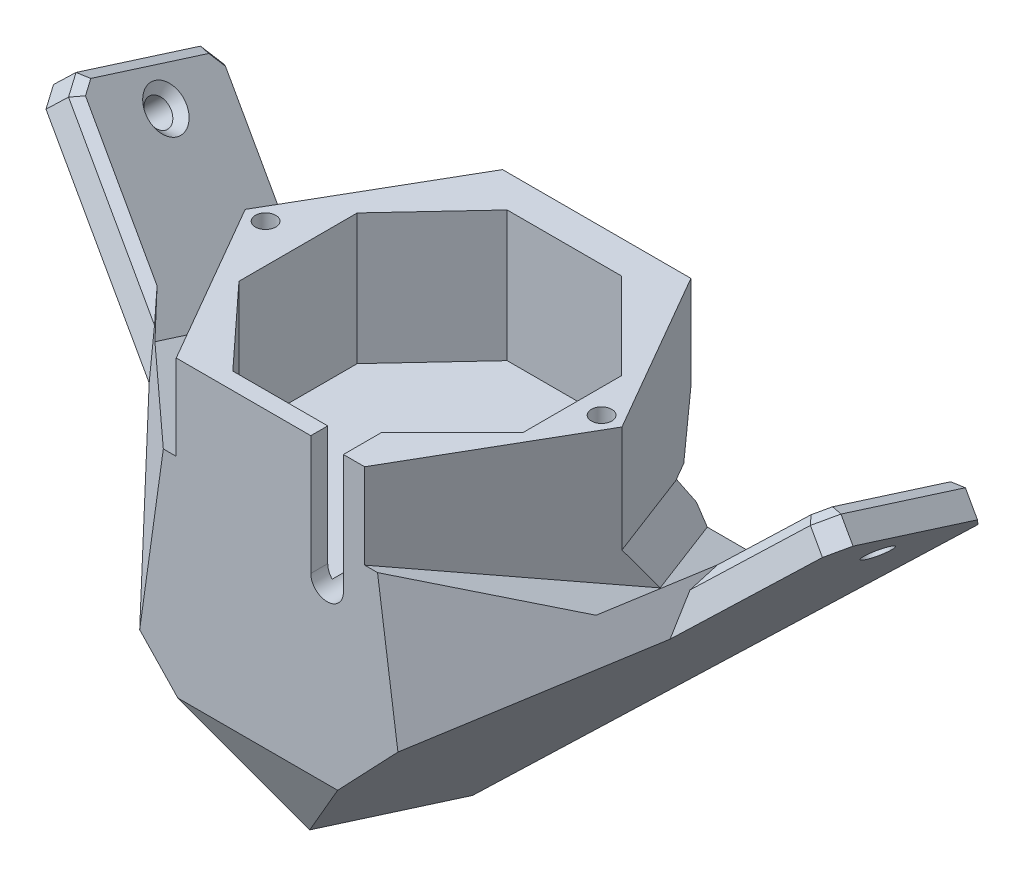
SolidWorks part; units mm, degrees
note: The reader was unsure of these and kept them because the rebuilt part matched: shared geometry of "Sketch4<3>", "Sketch7<2>".
ref_plane "Front Plane" through (0, 0, 0) normal (0, 0, 1) x (1, 0, 0)
ref_plane "Top Plane" through (0, 0, 0) normal (0, 1, 0) x (1, 0, 0)
ref_plane "Right Plane" through (0, 0, 0) normal (1, 0, 0) x (0, 0, -1)
sketch "Sketch4" plane through (0, 0, 0) normal (0, 1, 0) x (1, 0, 0)
  line L0 (7.1282, 21.2857) -> (35.6408, 21.2857) construction
  line L1 (12.3888, 35.3674) -> (26.3888, 35.3674)
  line L2 (26.3888, 35.3674) -> (36.9954, 24.7608)
  line L3 (36.9954, 24.7608) -> (36.9954, 12.7608)
  line L4 (36.9954, 12.7608) -> (25.6816, 1.4471)
  line L5 (25.6816, 1.4471) -> (12.6816, 1.4471)
  line L6 (12.6816, 1.4471) -> (3.52, 11.3625)
  line L7 (3.52, 11.3625) -> (3.52, 25.8625)
  line L8 (3.52, 25.8625) -> (12.3888, 35.3674)
  line L10 (42.4651, 19.3686) -> (30.9181, 39.3686)
  line L11 (30.9181, 39.3686) -> (7.8241, 39.3686)
  line L12 (7.8241, 39.3686) -> (-3.7229, 19.3686)
  line L13 (-3.7229, 19.3686) -> (7.8241, -0.6314)
  line L14 (7.8241, -0.6314) -> (30.9181, -0.6314)
  line L15 (30.9181, -0.6314) -> (42.4651, 19.3686)
  circle A0 centre (19.3711, 19.3686) radius 20 construction
  dimension "D1" = 14
  dimension "D2" = 15
  dimension "D3" = 12
  dimension "D4" = 16
  dimension "D5" = 13
  dimension "D6" = 13.5
  dimension "D7" = 14.5
  dimension "D8" = 13
  dimension "D9" = 40
extrude "Boss-Extrude3" add sketch "Sketch4" along normal blind 2 contours L8 L7 L6 L5 L4 L3 L2 L1 | L14 L15 L10 L11 L12 L13 L7 L8 L1 L2 L3 L4 L5 L6
extrude "Boss-Extrude4" add sketch "Sketch4<3>" along normal blind 18
sketch "Sketch4<3>" plane through (0, 0, 0) normal (0, 1, 0) x (1, 0, 0) same geometry as "Sketch4"
sketch "Sketch6" plane through (0, 0, 0.6314) normal (0, 0, 1) x (1, 0, 0)
  line L0 (26.3178, 3.3769) -> (26.3178, 18) construction
  line L1 (7.8241, 18) -> (30.9181, 18) construction
  line L2 (24.3178, 3.3769) -> (24.3178, 18)
  line L3 (28.3178, 3.3769) -> (28.3178, 18)
  arc A0 (24.3178, 3.3769) -> (28.3178, 3.3769) centre (26.3178, 3.3769) ccw
  arc A1 (28.3178, 18) -> (24.3178, 18) centre (26.3178, 18) ccw
  point P4 (26.3178, 10.6885)
  dimension "D1" = 4
extrude "Cut-Extrude2" cut sketch "Sketch6" against normal blind 6
fillet "Fillet2" radius 1 1 edges at (26.3178, 1.3769, -5.3686)
ref_plane "Plane1" through (0, 19.6843, -19.6843) normal (0, 0.7071, -0.7071) x (-1, 0, 0)
sketch "Sketch7" plane through (0, -8.893, -28.0813) normal (0, -0.3019, -0.9533) x (-1, 0, 0)
  line L0 (-17.8165, -27.1444) -> (-66.8226, 21.8617)
  line L1 (-229.9485, 184.9877) -> (-17.8165, -27.1444) construction
  line L2 (-66.8226, 21.8617) -> (-63.9942, 24.6902)
  line L3 (-63.9942, 24.6902) -> (-46.3165, 7.0125)
  line L4 (-46.3165, 7.0125) -> (10.6835, 7.0125)
  line L5 (10.6835, 7.0125) -> (28.3612, 24.6902)
  line L6 (28.3612, 24.6902) -> (31.1896, 21.8617)
  line L7 (-31.9586, -41.2865) -> (180.1734, 170.8455) construction
  line L8 (31.1896, 21.8617) -> (-17.8165, -27.1444)
  dimension "D1" = 4
  dimension "D2" = 4
  dimension "D3" = 25
  dimension "D4" = 25
  dimension "D5" = 57
extrude "Boss-Extrude5" add sketch "Sketch7" against normal up to vertex (13.9 mm away)
extrude "Boss-Extrude6" add sketch "Sketch7<2>" along normal up to surface (6.1 mm away)
sketch "Sketch7<2>" plane through (0, -8.893, -28.0813) normal (0, -0.3019, -0.9533) x (-1, 0, 0) same geometry as "Sketch7"
sketch "Sketch9" plane through (0, -10.7346, -33.8966) normal (0, -0.3019, -0.9533) x (-1, 0, 0)
  circle A0 centre (-18.7399, -5.0297) radius 76.2948
extrude "Cut-Extrude3" cut sketch "Sketch9" along normal blind 12
chamfer "Chamfer5" distance 15 angle 45 1 edges at (19.3711, 0, -23.2271)
chamfer "Chamfer6" distance 33 angle 45 1 edges at (19.3711, 0, -16.3172)
chamfer "Chamfer7" distance 10 angle 45 2 edges at (-0.8454, -6.1023, -14.3847) (39.9159, -4.3073, -14.9531)
chamfer "Chamfer8" distance 3 angle 45 2 edges at (37.6601, -1.4137, -27.6912) (1.0822, -1.4137, -27.6912)
extrude "Cut-Extrude4" cut sketch "Sketch10" against normal blind 15
sketch "Sketch10" plane through (0, 19, 0) normal (0, 1, 0) x (1, 0, 0)
  line L0 (-3.7229, 19.3686) -> (42.4651, 19.3686) construction
  circle A0 centre (-1.2229, 19.3686) radius 1.25
  circle A1 centre (39.9651, 19.3686) radius 1.25
extrude "Cut-Extrude5" cut sketch "Sketch11" against normal blind 10
sketch "Sketch11" plane through (35.322, -41.8699, -3.0575) normal (0.7071, 0.6741, -0.2135) x (0.7071, -0.6741, 0.2135)
  circle A0 centre (-85.0617, 10) radius 1.65
extrude "Cut-Extrude6" cut sketch "Sketch12" against normal blind 10
sketch "Sketch12" plane through (0.6719, -41.5258, -3.1665) normal (-0.7071, 0.6741, -0.2135) x (0.7071, 0.6741, -0.2135)
  circle A0 centre (84.5511, 10) radius 1.65
chamfer "Chamfer9" distance 2 angle 45 4 edges at (65.4084, 17.4934, -21.8571) (65.4084, 11.4552, -40.9239) (-29.7754, 17.4934, -21.8571) (-29.7754, 11.4552, -40.9239)
chamfer "Chamfer10" distance 1 angle 45 11 edges at (54.4482, 3.7029, -38.4688) (63.287, 12.4312, -40.184) (63.9942, 15.8225, -31.8175) (63.287, 17.8656, -23.0239) (57.4162, 12.5706, -20.2982) (-25.9642, 13.6462, -30.75) (-19.9004, 10.7756, -19.7297) (-27.6541, 17.8656, -23.0239) (-28.3612, 15.8225, -31.8175) (-27.6541, 12.4312, -40.184) (-18.8152, 3.7029, -38.4688)
chamfer "Chamfer11" distance 1 angle 45 1 edges at (59.3201, 11.2577, -30.75)
